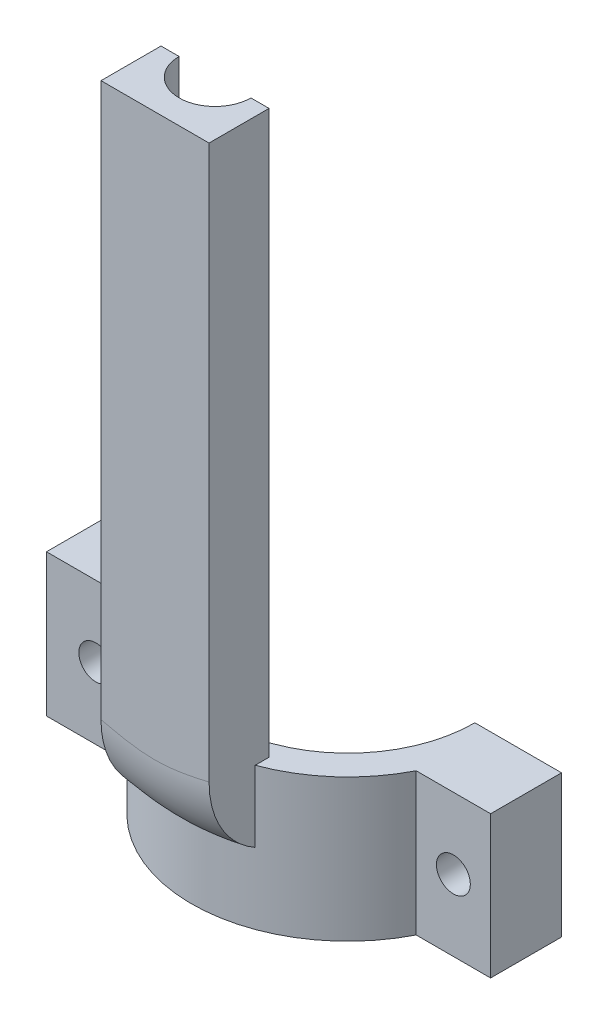
SolidWorks part; units mm, degrees
ref_plane "前基準面" through (0, 0, 0) normal (0, 0, 1) x (1, 0, 0)
ref_plane "上基準面" through (0, 0, 0) normal (0, 1, 0) x (1, 0, 0)
ref_plane "右基準面" through (0, 0, 0) normal (1, 0, 0) x (0, 0, -1)
sketch "草圖1" plane through (0, 0, 0) normal (0, 1, 0) x (1, 0, 0)
  circle A0 centre (0, 0) radius 14.34
  dimension "D1" = 28.68
extrude "伸長-薄件1" add sketch "草圖1" along normal blind 16.05 thin thin type one direction wall 3.29
ref_plane "平面1" through (17.75, 0, 0) normal (1, 0, 0) x (0, 0, -1)
sketch "草圖2" plane through (17.75, 0, 0) normal (1, 0, 0) x (0, 0, -1)
  line L0 (0, -983.95) -> (0, 49016.05) construction
  line L1 (14.34, 16.05) -> (-14.34, 16.05) construction
  line L2 (-1017.63, 8.025) -> (48982.37, 8.025) construction
  line L3 (-17.63, 16.05) -> (-17.63, 0) construction
  line L5 (-8, 16.05) -> (8, 16.05)
  line L6 (-8, 16.05) -> (-8, 0)
  line L7 (-8, 0) -> (8, 0)
  line L8 (8, 16.05) -> (8, 0)
  line L9 (-8, 16.05) -> (8, 0) construction
  line L10 (-8, 0) -> (8, 16.05) construction
  point P5 (0, 16.05)
  point P6 (0, 8.025)
  point P10 (-17.63, 8.025)
  dimension "D1" = 0
  dimension "D2" = 16
extrude "填料-伸長1" add sketch "草圖2" along normal blind 9.77 and the other way blind 3
sketch "草圖3" plane through (0, 16.05, 0) normal (0, 1, 0) x (1, 0, 0)
  line L0 (14.34, 0) -> (27.52, 0) construction
  line L1 (27.52, 8) -> (27.52, -8) construction
  line L2 (15.7104, -8) -> (27.52, -8) construction
  line L3 (27.52, 8) -> (24.11, 8)
  line L4 (27.52, 8) -> (27.52, -8)
  line L5 (27.52, -8) -> (24.11, -8)
  line L6 (24.11, 8) -> (24.11, -8)
  circle A0 centre (0, 0) radius 14.34 construction
  dimension "D1" = 3.41
extrude "除料-伸長1" cut sketch "草圖3" against normal through all
sketch "草圖4" plane through (0, 0, 8) normal (0, 0, 1) x (1, 0, 0)
  line L0 (19.9102, -983.95) -> (19.9102, 49016.05) construction
  line L1 (15.7104, 16.05) -> (24.11, 16.05) construction
  line L2 (-984.2896, 8.025) -> (49015.7104, 8.025) construction
  line L3 (15.7104, 0) -> (15.7104, 16.05) construction
  circle A0 centre (19.9102, 8.025) radius 1.91
  point P5 (19.9102, 16.05)
  point P10 (15.7104, 8.025)
  dimension "D1" = 3.82
extrude "除料-伸長2" cut sketch "草圖4" against normal through all
ref_plane "平面2" through (0, 0, 17.75) normal (0, 0, 1) x (1, 0, 0)
sketch "草圖5" plane through (0, 0, 17.75) normal (0, 0, 1) x (1, 0, 0)
  line L0 (-1017.63, 8.025) -> (48982.37, 8.025) construction
  line L1 (-17.63, 16.05) -> (-17.63, 0) construction
  line L2 (0, -983.95) -> (0, 49016.05) construction
  line L3 (14.34, 16.05) -> (-14.34, 16.05) construction
  line L5 (-6.095, 16.2886) -> (6.095, 16.2886)
  line L6 (-6.095, 16.2886) -> (-6.095, 8.025)
  line L7 (-6.095, 8.025) -> (6.095, 8.025)
  line L8 (6.095, 16.2886) -> (6.095, 8.025)
  line L9 (-6.095, 16.2886) -> (6.095, 8.025) construction
  line L10 (-6.095, 8.025) -> (6.095, 16.2886) construction
  point P5 (-17.63, 8.025)
  point P6 (0, 12.1568)
  point P10 (0, 16.05)
  dimension "D1" = 12.19
extrude "填料-伸長2" add sketch "草圖5" along normal blind 4 and the other way blind 2.77
sketch "草圖6" plane through (0, 16.2886, 0) normal (0, 1, 0) x (1, 0, 0)
  line L1 (-6.095, -14.98) -> (6.095, -14.98)
  line L2 (-6.095, -14.98) -> (-6.095, -21.75)
  line L3 (-6.095, -21.75) -> (6.095, -21.75)
  line L4 (6.095, -14.98) -> (6.095, -21.75)
extrude "填料-伸長3" add sketch "草圖6" along normal blind 63
sketch "草圖8" plane through (0, 79.2886, 0) normal (0, 1, 0) x (1, 0, 0)
  line L1 (-6.095, -21.75) -> (6.095, -21.75)
  line L2 (-6.095, -21.75) -> (-6.095, -14.98)
  line L3 (-6.095, -14.98) -> (6.095, -14.98)
  line L4 (6.095, -21.75) -> (6.095, -14.98)
extrude "填料-伸長4" add sketch "草圖8" along normal blind 0.16
ref_plane "平面3" through (-17.75, 0, 0) normal (1, 0, 0) x (0, 0, -1)
sketch "草圖12" plane through (-17.75, 0, 0) normal (1, 0, 0) x (0, 0, -1)
  line L0 (0.5435, -983.95) -> (0.5435, 49016.05) construction
  line L1 (17.63, 16.05) -> (-16.5429, 16.05) construction
  line L2 (-982.37, 8.025) -> (49017.63, 8.025) construction
  line L3 (17.63, 0) -> (17.63, 16.05) construction
  line L5 (8.5435, 16.05) -> (-7.4565, 16.05)
  line L6 (8.5435, 16.05) -> (8.5435, 0)
  line L7 (8.5435, 0) -> (-7.4565, 0)
  line L8 (-7.4565, 16.05) -> (-7.4565, 0)
  line L9 (8.5435, 16.05) -> (-7.4565, 0) construction
  line L10 (8.5435, 0) -> (-7.4565, 16.05) construction
  point P5 (0.5435, 16.05)
  point P6 (0.5435, 8.025)
  point P10 (17.63, 8.025)
  dimension "D1" = 0
  dimension "D2" = 16
extrude "填料-伸長5" add sketch "草圖12" along normal blind 3.16 and the other way blind 10
sketch "草圖13" plane through (0, 16.05, 0) normal (0, 1, 0) x (1, 0, 0)
  line L0 (-14.34, 0) -> (-27.75, 0) construction
  line L1 (-27.75, 8.5435) -> (-27.75, -7.4565) construction
  line L2 (-27.75, -7.4565) -> (-15.9755, -7.4565) construction
  line L3 (-27.75, 8.5435) -> (-26.54, 8.5435)
  line L4 (-27.75, 8.5435) -> (-27.75, -7.4565)
  line L5 (-27.75, -7.4565) -> (-26.54, -7.4565)
  line L6 (-26.54, 8.5435) -> (-26.54, -7.4565)
  circle A0 centre (0, 0) radius 14.34 construction
  dimension "D1" = 1.21
extrude "除料-伸長3" cut sketch "草圖13" against normal through all
sketch "草圖14" plane through (0, 0, -8.5435) normal (0, 0, -1) x (-1, 0, 0)
  line L0 (20.9808, -983.95) -> (20.9808, 49016.05) construction
  line L1 (26.54, 16.05) -> (15.4216, 16.05) construction
  line L2 (-973.46, 8.025) -> (49026.54, 8.025) construction
  line L3 (26.54, 0) -> (26.54, 16.05) construction
  circle A0 centre (20.9808, 8.025) radius 1.91
  point P5 (20.9808, 16.05)
  point P10 (26.54, 8.025)
  dimension "D1" = 3.82
extrude "除料-伸長4" cut sketch "草圖14" against normal through all
sketch "草圖15" plane through (0, 79.4486, 0) normal (0, 1, 0) x (1, 0, 0)
  line L0 (6.095, -14.98) -> (-6.095, -14.98) construction
  circle A0 centre (0, -14.98) radius 4.05
  dimension "D1" = 8.1
extrude "除料-伸長5" cut sketch "草圖15" against normal blind 24
sketch "草圖16" plane through (0, 16.05, 0) normal (0, 1, 0) x (1, 0, 0)
  line L0 (24.11, 8) -> (24.11, -8) construction
  line L1 (24.11, 0) -> (-32.2905, 0)
  line L2 (24.11, 0) -> (24.11, 19.935)
  line L3 (24.11, 19.935) -> (-32.2905, 19.935)
  line L4 (-32.2905, 0) -> (-32.2905, 19.935)
extrude "除料-伸長6" cut sketch "草圖16" against normal through all
fillet "圓角1" radius 10 1 edges at (0, 8.025, 21.75)
